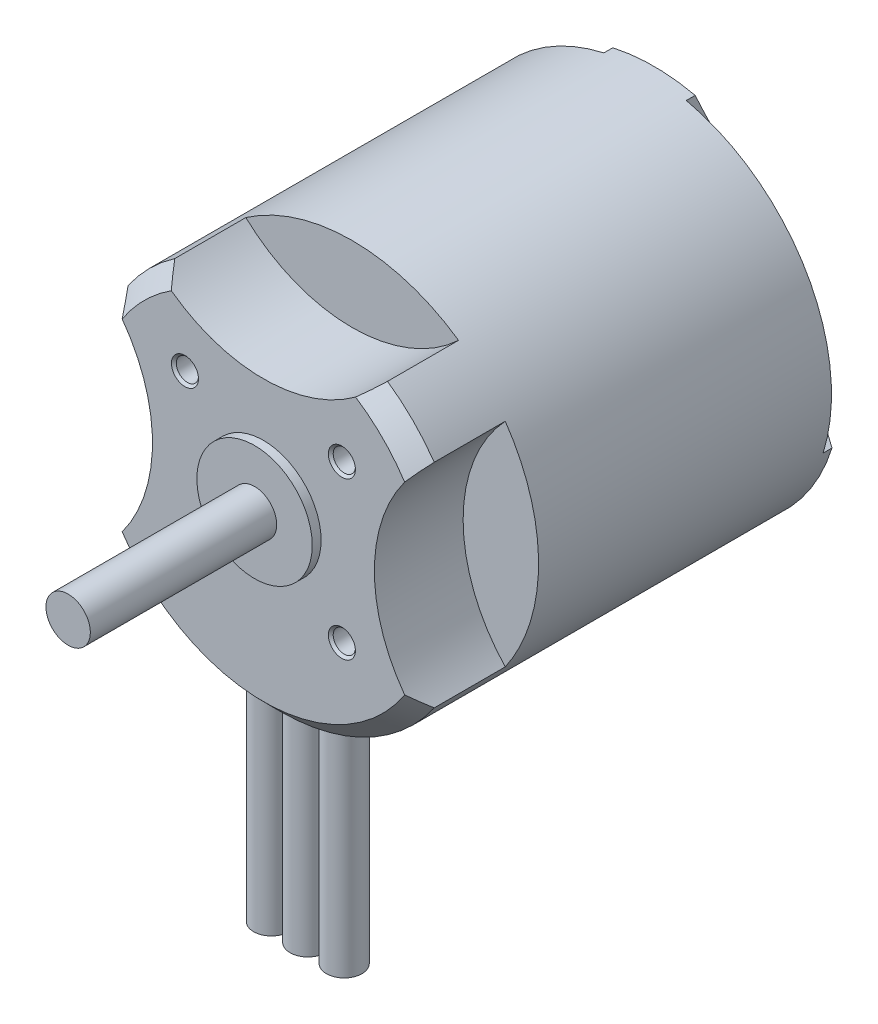
SolidWorks part; units mm, degrees
ref_plane "Front Plane" through (0, 0, 0) normal (0, 0, 1) x (1, 0, 0)
ref_plane "Top Plane" through (0, 0, 0) normal (0, 1, 0) x (1, 0, 0)
ref_plane "Right Plane" through (0, 0, 0) normal (1, 0, 0) x (0, 0, -1)
sketch "Sketch1" plane through (0, 0, 0) normal (0, 0, 1) x (1, 0, 0)
  circle A0 centre (0, 0) radius 21
  dimension "D1" = 42
extrude "Boss-Extrude1" add sketch "Sketch1" against normal blind 48
sketch "Sketch2" plane through (0, 0, 0) normal (0, 0, 1) x (1, 0, 0)
  circle A0 centre (0, 0) radius 2.5
  dimension "D1" = 5
extrude "Boss-Extrude2" add sketch "Sketch2" along normal blind 22
sketch "Sketch3" plane through (0, 0, 0) normal (0, 0, 1) x (1, 0, 0)
  line L0 (-8.8388, 8.8388) -> (0, 0) construction
  circle A0 centre (0, 0) radius 12.5 construction
  point P0 (-8.8388, 8.8388)
  point P4 (8.8388, 8.8388)
  point P5 (8.8388, -8.8388)
  point P6 (-8.8388, -8.8388)
  point P7 (0, 0)
  dimension "D2" = 25
  dimension "D3" = 45
  dimension "D1" = 4
sketch "Sketch4" plane through (0, 0, -48) normal (0, 0, -1) x (-1, 0, 0)
  point P0 (0, 7.5056)
  point P1 (6.5, -3.7528)
  point P5 (-6.5, -3.7528)
  point P6 (0, 0)
  dimension "D2" = 13
  dimension "D1" = 3
hole_wizard "M3x0.5 Tapped Hole1" positions "Sketch5" profile "Sketch6" tap size "M3x0.5" standard "ANSI Metric"
sketch "Sketch5" plane through (0, 0, 0) normal (0, 0, 1) x (1, 0, 0)
  point P0 (-8.8388, -8.8388)
  point P3 (-8.8388, 8.8388)
  point P6 (8.8388, 8.8388)
  point P9 (8.8388, -8.8388)
sketch "Sketch6" plane through (-8.8388, -8.8388, 0) normal (1, 0, 0) x (0, -1, 0)
  line L0 (0, 0) -> (0, 8.2511)
  line L1 (0, 8.2511) -> (1.25, 7.5)
  line L2 (1.25, 7.5) -> (1.25, 0.275)
  line L3 (1.25, 0.275) -> (1.525, 0)
  line L5 (1.525, 0) -> (0, 0)
  line L6 (-1.25, 0.275) -> (-1.525, 0) construction
  line L10 (0, 8.2511) -> (-1.25, 7.5) construction
  line L11 (0, -6.35) -> (0, 107.95) construction
  dimension "Tap Drill Dia." = 2.5
  dimension "Tap Drill Depth" = 7.5
  dimension "Near C'Sink Dia." = 3.05
  dimension "Near C'Sink Angle" = 90
  dimension "Drill Angle" = 118
cosmetic thread "Hole Thread1" parameters "D1"=6, "D2"=3
cosmetic thread "Hole Thread2" parameters "D1"=6, "D2"=3
cosmetic thread "Hole Thread3" parameters "D1"=6, "D2"=3
cosmetic thread "Hole Thread4" parameters "D1"=6, "D2"=3
hole_wizard "M3x0.5 Tapped Hole2" positions "Sketch7" profile "Sketch8" tap size "M3x0.5" standard "ANSI Metric"
sketch "Sketch7" plane through (0, 0, -48) normal (0, 0, -1) x (-1, 0, 0)
  point P0 (0, 7.5056)
  point P2 (6.5, -3.7528)
  point P5 (-6.5, -3.7528)
sketch "Sketch8" plane through (0, 7.5056, -48) normal (1, 0, 0) x (0, 1, 0)
  line L0 (0, 0) -> (0, 8.2511)
  line L1 (0, 8.2511) -> (1.25, 7.5)
  line L2 (1.25, 7.5) -> (1.25, 0.275)
  line L3 (1.25, 0.275) -> (1.525, 0)
  line L5 (1.525, 0) -> (0, 0)
  line L6 (-1.25, 0.275) -> (-1.525, 0) construction
  line L10 (0, 8.2511) -> (-1.25, 7.5) construction
  line L11 (0, -6.35) -> (0, 107.95) construction
  dimension "Tap Drill Dia." = 2.5
  dimension "Tap Drill Depth" = 7.5
  dimension "Near C'Sink Dia." = 3.05
  dimension "Near C'Sink Angle" = 90
  dimension "Drill Angle" = 118
cosmetic thread "Hole Thread5" parameters "D1"=6, "D2"=3
cosmetic thread "Hole Thread6" parameters "D1"=6, "D2"=3
cosmetic thread "Hole Thread7" parameters "D1"=6, "D2"=3
ref_axis "Axis1" through (0, 0, -48) along (0, 0, 1)
chamfer "Chamfer2" distance 8.5 distance2 4 1 edges at (21, 0, -48) first distance on face at (-1.525, 7.5056, -48)
sketch "Sketch9" plane through (0, 0, -48) normal (0, 0, -1) x (-1, 0, 0)
  line L0 (-34.641, 20) -> (0, 0) construction
  line L1 (23.1, 0) -> (-23.1, 0) construction
  circle A0 centre (-34.641, 20) radius 30
  circle A1 centre (34.641, 20) radius 30
  circle A2 centre (0, -40) radius 30
  circle A3 centre (-10.3923, 6) radius 3.5
  circle A4 centre (10.3923, 6) radius 3.5
  circle A5 centre (0, -12) radius 3.5
  point P12 (0, 0)
  point P20 (0, 0)
  circle M13 centre (0, 0) radius 12.5
  dimension "D2" = 40
  dimension "D3" = 60
  dimension "D6" = 7
  dimension "D1" = 30
  dimension "D5" = 12
  dimension "D4" = 3
  dimension "D7" = 3
extrude "Cut-Extrude1" cut sketch "Sketch9" against normal blind 5 contours A3 A0 M13 | A3 A0 M13 | L0 A0 A3 M13 | A0 L0 A3 | L0 A0 A3 | L0 A3 A0 M13 | A3 A0 M13 | L0 A3 M13 | A3 L0 M13 | A1 A4 | A5 A2 M13 | A5 A2 M13 | A5 A2 M13 | A5 M13 | A5 A2 M13 | A2 A5 | A3 | A1 region at (11.0786, 8.1386, -48) region at (34.9743, 20.1924, -48) region at (12.5875, 5.525, -48) region at (8.9277, 6.9937, -48) region at (10.5206, 4.2348, -48) region at (7.2735, 9.3106, -48) region at (11.6999, 1.6437, -48) region at (7.5729, 5.7157, -48) region at (8.7364, 3.7005, -48) region at (0, -40.3849, -48) region at (4.4264, -10.9543, -48) region at (-8.1547, 4.7081, -48) region at (0, -9.4162, -48) region at (0, -11.2285, -48) region at (0, -13.6636, -48) region at (-4.4264, -10.9543, -48)
sketch "Sketch10" plane through (0, 0, -48) normal (0, 0, -1) x (-1, 0, 0)
  circle A0 centre (0, 0) radius 5.5
  dimension "D1" = 11
extrude "Boss-Extrude3" add sketch "Sketch10" along normal blind 2
chamfer "Chamfer1" distance 1 angle 45 1 edges at (-5.5, 0, -50)
chamfer "Chamfer3" distance 2 angle 45 1 edges at (21, 0, 0)
sketch "Sketch11" plane through (0, 0, 0) normal (0, 0, 1) x (1, 0, 0)
  line L0 (-30, 0) -> (0, 0) construction
  circle A0 centre (-30, 0) radius 17.5
  circle A1 centre (0, 30) radius 17.5
  circle A2 centre (30, 0) radius 17.5
  point P5 (0, 0)
  point P6 (0, 0)
  point P10 (0, 0)
  point P12 (0, 0)
  dimension "D2" = 35
  dimension "D1" = 30
  dimension "D3" = 3
extrude "Cut-Extrude2" cut sketch "Sketch11" against normal blind 10
sketch "Sketch12" plane through (0, 0, 0) normal (0, 1, 0) x (1, 0, 0)
  line L0 (-4.1, 5) -> (0, 5) construction
  line L1 (0, 5) -> (4.1, 5) construction
  line L2 (0, 48) -> (0, 0) construction
  circle A0 centre (0, 5) radius 2
  circle A1 centre (-4.1, 5) radius 2
  circle A2 centre (4.1, 5) radius 2
  point P6 (-9.1688, -6.7415)
  point P7 (0, 0)
  point P8 (0, 5.5426)
  point P10 (0, 4.8444)
  dimension "D1" = 4
  dimension "D2" = 4.1
  dimension "D3" = 5
extrude "Boss-Extrude6" add sketch "Sketch12" against normal blind 45
sketch "Sketch13" plane through (0, 0, 0) normal (0, 0, 1) x (1, 0, 0)
  circle A0 centre (0, 0) radius 6.5
  dimension "D1" = 13
extrude "Boss-Extrude7" add sketch "Sketch13" along normal blind 1
